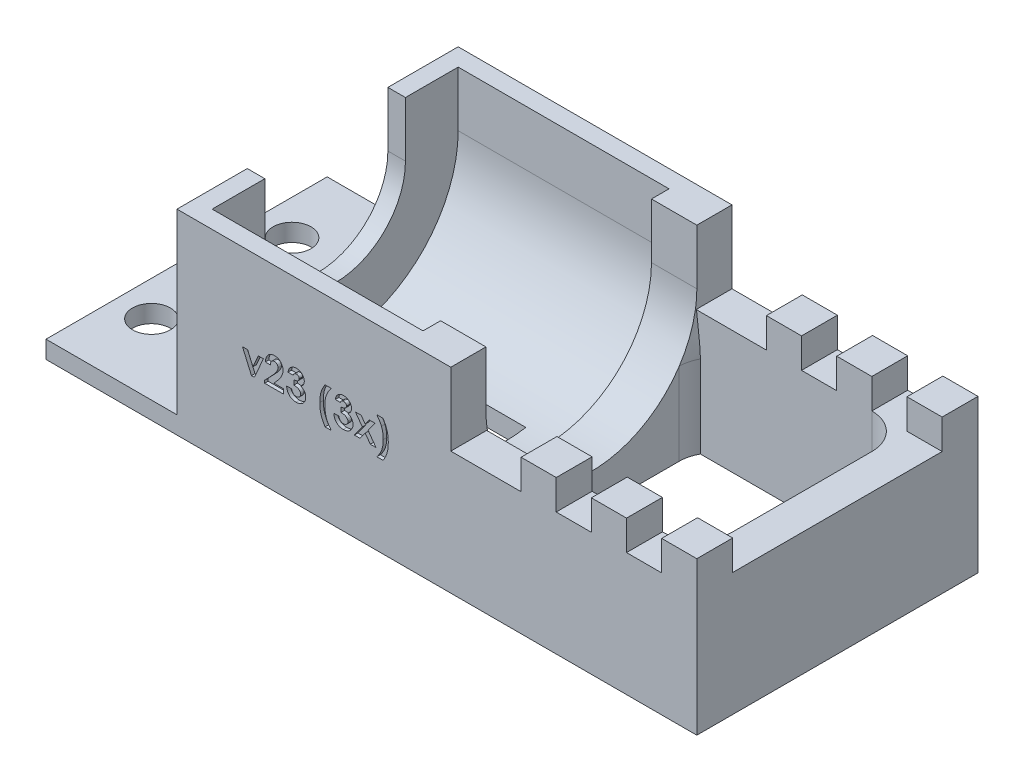
SolidWorks part; units mm, degrees
ref_plane "Front Plane" through (0, 0, 0) normal (0, 0, 1) x (1, 0, 0)
ref_plane "Top Plane" through (0, 0, 0) normal (0, 1, 0) x (1, 0, 0)
ref_plane "Right Plane" through (0, 0, 0) normal (1, 0, 0) x (0, 0, -1)
sketch "Sketch1" plane through (0, 0, 0) normal (0, 0, 1) x (1, 0, 0)
  line L1 (-76.2, -50.8) -> (76.2, -50.8)
  line L2 (-76.2, -50.8) -> (-76.2, 0)
  line L3 (-76.2, 0) -> (76.2, 0)
  line L4 (76.2, -50.8) -> (76.2, 0)
  line L5 (-76.2, -50.8) -> (76.2, 0) construction
  line L6 (-76.2, 0) -> (76.2, -50.8) construction
  point P0 (0, 0)
  dimension "D1" = 152.4
  dimension "D2" = 50.8
  dimension "D3" = 76.2
extrude "Boss-Extrude1" add sketch "Sketch1" along normal mid plane 50.8
sketch "Sketch2" plane through (0, 0, 0) normal (0, 0, 1) x (1, 0, 0)
  line L0 (-152.4829, -25.4) -> (19.6294, -25.4) construction
  line L1 (-49.3609, -3.175) -> (-49.3609, -12.7)
  line L2 (76.2, 0) -> (-76.2, 0) construction
  line L3 (76.2, 0) -> (-76.2, 0) construction
  line L4 (-11.2609, -3.175) -> (-11.2609, -6.35)
  line L5 (-11.2609, -25.4) -> (-11.2609, -3.175) construction
  line L6 (-128.4172, -25.4) -> (-157.8092, -25.4)
  line L7 (19.6294, -25.4) -> (20.7431, -25.4)
  line L8 (-607.3619, -25.4) -> (19.6294, -25.4) construction
  line L9 (-49.3609, -3.175) -> (-11.2609, -3.175)
  line L10 (19.6294, -25.4) -> (-128.4172, -25.4)
  line L11 (-11.2609, -6.35) -> (-4.6569, -6.35)
  line L12 (-4.6569, -6.35) -> (-4.6569, -15.494)
  line L13 (-4.6569, -15.494) -> (20.7431, -15.494)
  line L14 (-49.3609, -12.7) -> (-220.2024, -12.7)
  line L15 (-220.2024, -12.7) -> (-220.2024, -25.4)
  line L16 (-220.2024, -25.4) -> (-157.8092, -25.4)
  line L20 (20.7431, -15.494) -> (20.7431, -25.4)
  line L21 (-76.2, 0) -> (-76.2, -50.8) construction
  point P23 (-11.2609, -25.4)
  dimension "D1" = 22.225
  dimension "D2" = 38.1
  dimension "D3" = 25.4
  dimension "D4" = 32.004
  dimension "D5" = 9.906
  dimension "D6" = 3.175
  dimension "D7" = 26.8391
  dimension "D8" = 25.4
  dimension "D9" = 12.7
revolve "Cut-Revolve1" cut sketch "Sketch2" angle 360 about L0
sketch "Sketch38" plane through (20.7431, 0, 0) normal (1, 0, 0) x (0, 0, -1)
  line L1 (-10, -35.4) -> (10, -35.4)
  line L2 (-10, -35.4) -> (-10, -15.4)
  line L3 (-10, -15.4) -> (10, -15.4)
  line L4 (10, -35.4) -> (10, -15.4)
  line L5 (-10, -35.4) -> (10, -15.4) construction
  line L6 (-10, -15.4) -> (10, -35.4) construction
  circle A0 centre (0, -25.4) radius 9.906 construction
  point P1 (0, -25.4)
  dimension "D1" = 20
  dimension "D2" = 20
extrude "Cut-Extrude33" cut sketch "Sketch38" against normal offset from surface (23.8125 mm away) 1.5875 up to face at (-4.6569, -25.4, 19.05)
sketch "Sketch37" plane through (76.2, 0, 0) normal (1, 0, 0) x (0, 0, -1)
  line L0 (25.4, -50.8) -> (25.4, 0) construction
  line L1 (-25.4, 0) -> (25.4, 0)
  line L2 (-25.4, 0) -> (-25.4, -25.4)
  line L3 (-25.4, -25.4) -> (25.4, -25.4)
  line L4 (25.4, 0) -> (25.4, -25.4)
  line L5 (10, -35.4) -> (10, -15.4) construction
  point P7 (0, -25.4)
  point P11 (0, 0)
  point P14 (10, -25.4)
extrude "Cut-Extrude32" cut sketch "Sketch37" against normal through all
sketch "Sketch39" plane through (0, -25.4, 0) normal (0, 1, 0) x (1, 0, 0)
  line L24 (-49.3609, -12.7) -> (-76.2, -12.7)
  line L25 (-76.2, -12.7) -> (-76.2, -25.4)
  line L26 (-76.2, -25.4) -> (76.2, -25.4)
  line L27 (76.2, -25.4) -> (76.2, 25.4)
  line L28 (76.2, 25.4) -> (-76.2, 25.4)
  line L29 (-76.2, 25.4) -> (-76.2, 12.7)
  line L30 (-76.2, 12.7) -> (-49.3609, 12.7)
  line L31 (-49.3609, 12.7) -> (-49.3609, 22.225)
  line L32 (-49.3609, 22.225) -> (-11.2609, 22.225)
  line L33 (-11.2609, 22.225) -> (-11.2609, 19.05)
  line L34 (-11.2609, 19.05) -> (-4.6569, 19.05)
  line L35 (-4.6569, 19.05) -> (-4.6569, 9.906)
  line L36 (-4.6569, 9.906) -> (-3.0694, 9.906)
  line L37 (-3.0694, 9.906) -> (-3.0694, 10)
  line L38 (-3.0694, 9.906) -> (-3.0694, 10)
  line L39 (20.7431, 10) -> (20.7431, -10)
  line L40 (-3.0694, 10) -> (20.7431, 10)
  line L41 (-3.0694, 10) -> (20.7431, 10)
  line L42 (-3.0694, -9.906) -> (-4.6569, -9.906)
  line L43 (-4.6569, -9.906) -> (-4.6569, -19.05)
  line L44 (-4.6569, -19.05) -> (-11.2609, -19.05)
  line L45 (-11.2609, -19.05) -> (-11.2609, -22.225)
  line L46 (-11.2609, -22.225) -> (-49.3609, -22.225)
  line L47 (-49.3609, -22.225) -> (-49.3609, -12.7)
  line L48 (-49.3609, -12.7) -> (-76.2, -12.7)
  line L49 (-76.2, -12.7) -> (-76.2, -25.4)
  line L50 (-76.2, -25.4) -> (76.2, -25.4)
  line L51 (76.2, -25.4) -> (76.2, 25.4)
  line L52 (76.2, 25.4) -> (-76.2, 25.4)
  line L53 (-76.2, 25.4) -> (-76.2, 12.7)
  line L54 (-76.2, 12.7) -> (-49.3609, 12.7)
  line L55 (-49.3609, 12.7) -> (-49.3609, 22.225)
  line L56 (-49.3609, 22.225) -> (-11.2609, 22.225)
  line L57 (-11.2609, 22.225) -> (-11.2609, 19.05)
  line L58 (-11.2609, 19.05) -> (-4.6569, 19.05)
  line L59 (-4.6569, 19.05) -> (-4.6569, 9.906)
  line L60 (-4.6569, 9.906) -> (-3.0694, 9.906)
  line L61 (20.7431, -10) -> (-3.0694, -10)
  line L62 (20.7431, -10) -> (-3.0694, -10)
  line L63 (20.7431, 10) -> (20.7431, -10)
  line L64 (-3.0694, -10) -> (-3.0694, -9.906)
  line L65 (-3.0694, -10) -> (-3.0694, -9.906)
  line L66 (-3.0694, -9.906) -> (-4.6569, -9.906)
  line L67 (-4.6569, -9.906) -> (-4.6569, -19.05)
  line L68 (-4.6569, -19.05) -> (-11.2609, -19.05)
  line L69 (-11.2609, -19.05) -> (-11.2609, -22.225)
  line L70 (-11.2609, -22.225) -> (-49.3609, -22.225)
  line L71 (-49.3609, -22.225) -> (-49.3609, -12.7)
  dimension "D1" = 0
extrude "Boss-Extrude5" add sketch "Sketch39" along normal blind 25.4
ref_axis "Axis1" through (-3.0694, -25.4, 0) along (-1, 0, 0)
ref_plane "Plane_Mid" through (0, -25.4, 0) normal (0, 1, 0) x (1, 0, 0)
sketch "Sketch45" plane through (0, 0, 0) normal (0, 0, 1) x (1, 0, 0)
  line L2 (76.2, 0) -> (-3.0694, 0)
  line L4 (76.2, 0) -> (76.2, -19.05)
  line L5 (76.2, -19.05) -> (-3.0694, -19.05)
  line L6 (-3.0694, -25.4) -> (-4.6569, -25.4) construction
  line L8 (-3.0694, 0) -> (-3.0694, -19.05)
  dimension "D2" = 6.35
extrude "Cut-Extrude54" cut sketch "Sketch45" against normal through all both and the other way through all
sketch "Sketch53" plane through (20.7431, 0, 0) normal (-1, 0, 0) x (0, 0, 1)
  circle A0 centre (0, -25.4) radius 2
  dimension "D1" = 4
extrude "Cut-Extrude46" cut sketch "Sketch53" against normal blind 0.0254
sketch "Sketch72" plane through (0, -19.05, 0) normal (0, 1, 0) x (1, 0, 0)
  line L0 (-3.0694, -25.4) -> (-3.0694, -13.175)
  line L1 (-3.0694, -10) -> (-3.0694, -25.4) construction
  line L2 (-3.0694, -13.175) -> (23.9181, -13.175)
  line L3 (23.9181, -13.175) -> (23.9181, 13.175)
  line L4 (23.9181, 13.175) -> (-3.0694, 13.175)
  line L5 (-3.0694, 25.4) -> (-3.0694, 10) construction
  line L6 (-3.0694, 13.175) -> (-3.0694, 25.4)
  line L7 (-3.0694, 25.4) -> (76.2, 25.4)
  line L8 (76.2, 25.4) -> (76.2, -25.4)
  line L9 (76.2, -25.4) -> (-3.0694, -25.4)
  line L10 (-3.0694, -10) -> (20.7431, -10) construction
  line L11 (-3.0694, -10) -> (-3.0694, -13.175) construction
  line L12 (20.7431, -10) -> (23.9181, -10) construction
  line L13 (20.7431, 10) -> (20.7431, 13.175) construction
  dimension "D1" = 3.175
sketch "Sketch61" plane through (-4.6569, 0, 0) normal (-1, 0, 0) x (0, 0, 1)
  circle A0 centre (0, -25.4) radius 9.525
  circle A1 centre (0, -25.4) radius 9.906
  arc A2 (-9.906, -25.4) -> (9.906, -25.4) centre (0, -25.4) ccw construction
  dimension "D1" = 19.05
extrude "Boss-Extrude11" add sketch "Sketch61" against normal up to surface (1.5875 mm away) up to face at (-3.0694, -17.3088, 0)
sketch "Sketch70" plane through (0, 0, 0) normal (0, 1, 0) x (1, 0, 0)
  line L1 (-4.6569, 9.906) -> (-3.0694, 9.906)
  line L2 (-4.6569, 9.906) -> (-4.6569, -9.906)
  line L3 (-4.6569, -9.906) -> (-3.0694, -9.906)
  line L4 (-3.0694, 9.906) -> (-3.0694, -9.906)
extrude "Boss-Extrude17" add sketch "Sketch70" against normal up to next
sketch "Sketch76" plane through (0, -35.4, 0) normal (0, 1, 0) x (1, 0, 0)
  line L5 (-3.0694, -10) -> (20.7431, -10)
  line L6 (20.7431, -10) -> (20.7431, 10)
  line L9 (20.7431, 10) -> (-3.0694, 10)
  line L10 (-3.0694, 10) -> (-3.0694, -10)
  line L11 (-3.0694, -10) -> (20.7431, -10)
  line L12 (20.7431, -10) -> (20.7431, 10)
  line L13 (20.7431, 10) -> (-3.0694, 10)
  line L14 (-3.0694, 10) -> (-3.0694, -10)
  dimension "D1" = 0
extrude "Cut-Extrude58" cut sketch "Sketch76" against normal through all
sketch "Sketch86" plane through (0, -19.05, 0) normal (0, 1, 0) x (1, 0, 0)
  line L8 (-3.0694, -25.4) -> (76.2, -25.4)
  line L9 (-3.0694, -25.4) -> (76.2, -25.4)
  line L10 (76.2, -25.4) -> (76.2, 25.4)
  line L11 (76.2, -25.4) -> (76.2, 25.4)
  line L12 (76.2, 25.4) -> (-3.0694, 25.4)
  line L13 (76.2, 25.4) -> (-3.0694, 25.4)
  line L16 (20.7431, 10) -> (20.7431, -10)
  line L25 (20.7431, -10) -> (-3.0694, -10)
  line L26 (-3.0694, -10) -> (-3.0694, -25.4)
  line L30 (-3.0694, 25.4) -> (-3.0694, 10)
  line L31 (-3.0694, 10) -> (20.7431, 10)
  line L32 (20.7431, 10) -> (20.7431, -10)
  line L41 (20.7431, -10) -> (-3.0694, -10)
  line L42 (-3.0694, -10) -> (-3.0694, -25.4)
  line L46 (-3.0694, 25.4) -> (-3.0694, 10)
  line L47 (-3.0694, 10) -> (20.7431, 10)
  dimension "D1" = 0
extrude "Boss-Extrude24" add sketch "Sketch86" along normal blind 3.175
ref_plane "Plane1" through (-74.7609, 0, 0) normal (1, 0, 0) x (0, 0, -1)
sketch "Sketch89" plane through (0, 0, 0) normal (0, 1, 0) x (1, 0, 0)
  line L0 (-3.0694, 0) -> (-4.6569, 0) construction
  line L1 (-38.3605, -3.81) -> (-18.7213, -3.81)
  line L2 (-38.3605, -3.81) -> (-38.3605, 3.81)
  line L3 (-38.3605, 3.81) -> (-18.7213, 3.81)
  line L4 (-18.7213, -3.81) -> (-18.7213, 3.81)
  line L5 (-38.3605, -3.81) -> (-18.7213, 3.81) construction
  line L6 (-38.3605, 3.81) -> (-18.7213, -3.81) construction
  point P4 (-28.5409, 0)
extrude "Cut-Extrude64" cut sketch "Sketch89" against normal through all both and the other way through all
sketch "Sketch77" plane through (0, 0, 0) normal (0, 0, 1) x (1, 0, 0)
  line L0 (20.7431, -24.0284) -> (23.9181, -24.0284)
  line L1 (-3.0694, -26.7716) -> (20.7431, -26.7716)
  line L2 (-3.0694, -26.7716) -> (-3.0694, -24.0284)
  line L3 (-3.0694, -24.0284) -> (20.7431, -24.0284)
  line L4 (20.7431, -26.7716) -> (20.7431, -24.0284) construction
  line L5 (-3.0694, -26.7716) -> (20.7431, -24.0284) construction
  line L6 (-3.0694, -24.0284) -> (20.7431, -26.7716) construction
  line L7 (23.9181, -24.0284) -> (23.9181, -26.7716)
  line L8 (23.9181, -26.7716) -> (20.7431, -26.7716)
  line L9 (-3.0694, -25.4) -> (-4.6569, -25.4) construction
  line L10 (-3.0694, -15.875) -> (-3.0694, -50.8) construction
  line L11 (20.7431, -15.875) -> (20.7431, -50.8) construction
  point P0 (8.8368, -25.4)
  dimension "D1" = 3.175
  dimension "D2" = 2.7432
extrude "Cut-Extrude59" cut sketch "Sketch77" against normal through all both and the other way through all
sketch "Sketch96" plane through (0, 0, 25.4) normal (0, 0, 1) x (1, 0, 0)
  line L0 (-39.6347, 0) -> (-39.6347, -50.8) construction
  line L1 (-76.2, 0) -> (-3.0694, 0) construction
  line L2 (-76.2, -50.8) -> (76.2, -50.8) construction
  line L3 (-55.5097, -15.4427) -> (-23.7597, -15.4427)
  arc A0 (-23.7597, -15.4427) -> (-55.5097, -15.4427) centre (-39.6347, -32.1115) ccw
  point P8 (-39.6347, -15.4427)
  point P10 (-39.6347, -9.0927)
  dimension "D2" = 6.35
  dimension "D1" = 31.75
extrude "Cut-Extrude71" cut sketch "Sketch96" against normal through all
sketch "Sketch97" plane through (0, 0, 0) normal (0, 1, 0) x (1, 0, 0)
  line L0 (-76.2, -25.4) -> (-3.0694, -25.4) construction
  line L1 (-76.2, 25.4) -> (-52.5359, 25.4)
  line L2 (-76.2, 25.4) -> (-76.2, -25.4)
  line L3 (-76.2, -25.4) -> (-52.5359, -25.4)
  line L4 (-52.5359, 25.4) -> (-52.5359, -25.4)
  line L5 (-49.3609, 12.7) -> (-49.3609, 22.225) construction
  dimension "D1" = 3.175
extrude "Cut-Extrude72" cut sketch "Sketch97" against normal offset from surface (47.625 mm away) 3.175 up to face at (-28.5409, -50.8, 0)
sketch "Sketch98" plane through (0, -47.625, 0) normal (0, 1, 0) x (1, 0, 0)
  line L0 (-76.2, -25.4) -> (-76.2, 25.4) construction
  circle A0 centre (-69.85, 12.7) radius 3.429
  circle A1 centre (-57.15, 12.7) radius 3.429
  circle A2 centre (-57.15, 0) radius 3.429
  circle A3 centre (-57.15, -12.7) radius 3.429
  circle A4 centre (-69.85, 0) radius 3.429
  circle A5 centre (-69.85, -12.7) radius 3.429
  dimension "D1" = 6.858
  dimension "D2" = 76.2
  dimension "D3" = 6.35
  dimension "D4" = 12.7
  dimension "D5" = 2
  dimension "D6" = 3
extrude "Cut-Extrude73" cut sketch "Sketch98" against normal through all
ref_plane "Plane2" through (0, -25.4, 0) normal (0, 1, 0) x (1, 0, 0)
sketch "Sketch99" plane through (0, -25.4, 0) normal (0, 1, 0) x (1, 0, 0)
  line L1 (-3.0694, -25.4) -> (76.2, -25.4)
  line L2 (-3.0694, -25.4) -> (-3.0694, 25.4)
  line L3 (-3.0694, 25.4) -> (76.2, 25.4)
  line L4 (76.2, -25.4) -> (76.2, 25.4)
extrude "Cut-Extrude74" cut sketch "Sketch99" along normal through all
sketch "Sketch100" plane through (0, -25.4, 0) normal (0, 1, 0) x (1, 0, 0)
  line L0 (-3.0694, -25.4) -> (23.9181, -25.4) construction
  line L1 (-3.0694, -25.4) -> (76.2, -25.4)
  line L2 (-3.0694, -25.4) -> (-3.0694, 25.4)
  line L3 (-3.0694, 25.4) -> (76.2, 25.4)
  line L4 (76.2, -25.4) -> (76.2, 25.4)
  line L5 (-3.0694, 25.4) -> (76.2, 25.4) construction
  line L6 (-3.0694, -10) -> (-3.0694, -25.4) construction
extrude "Cut-Extrude75" cut sketch "Sketch100" against normal blind 2.2225
sketch "Sketch101" plane through (0, -25.4, 0) normal (0, 1, 0) x (1, 0, 0)
  line L0 (-3.0694, 25.4) -> (76.2, 25.4) construction
  line L1 (47.7306, 25.4) -> (52.3026, 25.4)
  line L2 (47.7306, 25.4) -> (47.7306, -25.4)
  line L3 (47.7306, -25.4) -> (52.3026, -25.4)
  line L4 (52.3026, 25.4) -> (52.3026, -25.4)
  line L6 (-3.0694, -25.4) -> (-3.0694, -13.175) construction
  dimension "D1" = 4.572
  dimension "D2" = 50.8
extrude "Cut-Extrude76" cut sketch "Sketch101" against normal blind 6.0579
sketch "Sketch103" plane through (0, -27.6225, 0) normal (0, 1, 0) x (1, 0, 0)
  line L0 (-3.0694, -25.4) -> (-3.0694, -13.175) construction
  line L1 (-3.0694, 0) -> (-4.6569, 0) construction
  line L2 (41.3806, 22.225) -> (-3.0694, 22.225)
  line L3 (41.3806, 22.225) -> (41.3806, -22.225)
  line L4 (41.3806, -22.225) -> (-3.0694, -22.225)
  line L5 (-3.0694, 22.225) -> (-3.0694, -22.225)
  line L6 (-3.0694, 25.4) -> (76.2, 25.4) construction
  line L7 (47.7306, -25.4) -> (47.7306, 25.4) construction
  point P6 (41.3806, 0)
  dimension "D1" = 3.175
  dimension "D2" = 6.35
extrude "Cut-Extrude78" cut sketch "Sketch103" against normal through all
sketch "Sketch104" plane through (-4.6569, 0, 0) normal (-1, 0, 0) x (0, 0, 1)
  line L3 (19.05, -25.4) -> (19.05, 0)
  line L4 (19.05, 0) -> (-19.05, 0)
  line L5 (-19.05, 0) -> (-19.05, -25.4)
  line L6 (19.05, -25.4) -> (19.05, 0)
  line L7 (19.05, 0) -> (-19.05, 0)
  line L8 (-19.05, 0) -> (-19.05, -25.4)
  arc A1 (-19.05, -25.4) -> (19.05, -25.4) centre (0, -25.4) ccw
  arc A2 (-19.05, -25.4) -> (19.05, -25.4) centre (0, -25.4) ccw
  dimension "D1" = 0
extrude "Cut-Extrude79" cut sketch "Sketch104" against normal up to next
sketch "Sketch105" plane through (0, -50.8, 0) normal (0, 1, 0) x (1, 0, 0)
  line L0 (41.3806, 22.225) -> (-3.0694, 22.225) construction
  line L1 (-3.0694, 22.225) -> (41.3806, 22.225)
  line L2 (-3.0694, 22.225) -> (-3.0694, 47.625)
  line L3 (-3.0694, 47.625) -> (41.3806, 47.625)
  line L4 (41.3806, 22.225) -> (41.3806, 47.625)
  line L5 (0, 0) -> (31.7243, 0) construction
  line L6 (-3.0694, 19.05) -> (-3.0694, 25.4) construction
  line L7 (41.3806, -22.225) -> (41.3806, 22.225) construction
  line L8 (41.3806, -22.225) -> (41.3806, -47.625)
  line L9 (-3.0694, -47.625) -> (41.3806, -47.625)
  line L10 (-3.0694, -22.225) -> (-3.0694, -47.625)
  line L11 (-3.0694, -22.225) -> (41.3806, -22.225)
  dimension "D1" = 25.4
extrude "Boss-Extrude25" add sketch "Sketch105" along normal up to surface (23.1775 mm away) up to face at (20.7431, -27.6225, 0)
sketch "Sketch106" plane through (0, -27.6225, 0) normal (0, 1, 0) x (1, 0, 0)
  line L0 (76.2, 25.4) -> (52.3026, 25.4) construction
  line L1 (76.2, 25.4) -> (58.6526, 25.4)
  line L2 (76.2, 25.4) -> (76.2, -25.4)
  line L3 (76.2, -25.4) -> (58.6526, -25.4)
  line L4 (58.6526, 25.4) -> (58.6526, -25.4)
  line L5 (76.2, -25.4) -> (76.2, 25.4) construction
  line L6 (52.3026, -25.4) -> (76.2, -25.4) construction
  line L7 (52.3026, -25.4) -> (52.3026, 25.4) construction
  dimension "D1" = 6.35
extrude "Cut-Extrude80" cut sketch "Sketch106" against normal through all
fillet "Fillet1" radius 6.35 14 edges at (-3.0694, -39.2112, -47.625) (41.3806, -39.2112, -47.625) (41.3806, -39.2112, -25.4) (58.6526, -39.2112, -25.4) (58.6526, -39.2112, 25.4) (41.3806, -39.2112, 25.4) (41.3806, -39.2112, 47.625) (-3.0694, -39.2112, 47.625) (-3.0694, -39.2112, 25.4) (-3.0694, -39.2112, 22.225) (-3.0694, -39.2112, -22.225) (41.3806, -39.2112, -22.225) (41.3806, -39.2112, 22.225) (-3.0694, -39.2112, -25.4)
sketch "Sketch107" plane through (0, -27.6225, 0) normal (0, 1, 0) x (1, 0, 0)
  line L0 (47.7306, -25.4) -> (47.7306, 25.4) construction
  line L1 (22.3306, 47.625) -> (47.7306, 47.625)
  line L2 (22.3306, 47.625) -> (22.3306, 6.35)
  line L3 (22.3306, 6.35) -> (47.7306, 6.35)
  line L4 (47.7306, 47.625) -> (47.7306, 6.35)
  line L5 (3.2806, 47.625) -> (35.0306, 47.625) construction
  line L6 (0, 0) -> (41.3806, 0) construction
  line L7 (41.3806, -15.875) -> (41.3806, 15.875) construction
  line L8 (47.7306, -47.625) -> (47.7306, -6.35)
  line L9 (22.3306, -6.35) -> (47.7306, -6.35)
  line L10 (22.3306, -47.625) -> (22.3306, -6.35)
  line L11 (22.3306, -47.625) -> (47.7306, -47.625)
  dimension "D1" = 25.4
  dimension "D2" = 6.35
extrude "Cut-Extrude81" cut sketch "Sketch107" against normal up to surface (3.8354 mm away) up to face at (50.0166, -31.4579, 0)
sketch "Sketch108" plane through (0, -15.4427, 0) normal (0, 1, 0) x (1, 0, 0)
  line L0 (-52.5359, -25.4) -> (-23.7597, -25.4) construction
  line L1 (-52.5359, -25.4) -> (14.8431, -25.4)
  line L2 (-52.5359, -25.4) -> (-52.5359, 39.7712)
  line L3 (-52.5359, 39.7712) -> (14.8431, 39.7712)
  line L4 (14.8431, -25.4) -> (14.8431, 39.7712)
extrude "Cut-Extrude82" cut sketch "Sketch108" along normal through all
sketch "Sketch109" plane through (0, -31.4579, 0) normal (0, 1, 0) x (1, 0, 0)
  line L16 (52.3026, 25.4) -> (47.7306, 25.4)
  line L17 (41.3806, 31.75) -> (41.3806, 41.275)
  line L18 (35.0306, 47.625) -> (22.3306, 47.625)
  line L19 (22.3306, 47.625) -> (22.3306, 22.225)
  line L20 (22.3306, 22.225) -> (35.0306, 22.225)
  line L21 (41.3806, 15.875) -> (41.3806, 6.35)
  line L22 (41.3806, 6.35) -> (47.7306, 6.35)
  line L23 (47.7306, 6.35) -> (47.7306, -6.35)
  line L24 (47.7306, -6.35) -> (41.3806, -6.35)
  line L25 (41.3806, -6.35) -> (41.3806, -15.875)
  line L26 (35.0306, -22.225) -> (22.3306, -22.225)
  line L27 (22.3306, -22.225) -> (22.3306, -47.625)
  line L28 (22.3306, -47.625) -> (35.0306, -47.625)
  line L29 (41.3806, -41.275) -> (41.3806, -31.75)
  line L30 (47.7306, -25.4) -> (52.3026, -25.4)
  line L31 (52.3026, -25.4) -> (52.3026, 25.4)
  line L32 (52.3026, 25.4) -> (47.7306, 25.4)
  line L33 (41.3806, 31.75) -> (41.3806, 41.275)
  line L34 (35.0306, 47.625) -> (22.3306, 47.625)
  line L35 (22.3306, 47.625) -> (22.3306, 22.225)
  line L36 (22.3306, 22.225) -> (35.0306, 22.225)
  line L37 (41.3806, 15.875) -> (41.3806, 6.35)
  line L38 (41.3806, 6.35) -> (47.7306, 6.35)
  line L39 (47.7306, 6.35) -> (47.7306, -6.35)
  line L40 (47.7306, -6.35) -> (41.3806, -6.35)
  line L41 (41.3806, -6.35) -> (41.3806, -15.875)
  line L42 (35.0306, -22.225) -> (22.3306, -22.225)
  line L43 (22.3306, -22.225) -> (22.3306, -47.625)
  line L44 (22.3306, -47.625) -> (35.0306, -47.625)
  line L45 (41.3806, -41.275) -> (41.3806, -31.75)
  line L46 (47.7306, -25.4) -> (52.3026, -25.4)
  line L47 (52.3026, -25.4) -> (52.3026, 25.4)
  arc A6 (41.3806, 31.75) -> (47.7306, 25.4) centre (47.7306, 31.75) ccw
  arc A7 (41.3806, 41.275) -> (35.0306, 47.625) centre (35.0306, 41.275) ccw
  arc A8 (41.3806, 15.875) -> (35.0306, 22.225) centre (35.0306, 15.875) ccw
  arc A9 (35.0306, -22.225) -> (41.3806, -15.875) centre (35.0306, -15.875) ccw
  arc A10 (35.0306, -47.625) -> (41.3806, -41.275) centre (35.0306, -41.275) ccw
  arc A11 (47.7306, -25.4) -> (41.3806, -31.75) centre (47.7306, -31.75) ccw
  arc A12 (41.3806, 31.75) -> (47.7306, 25.4) centre (47.7306, 31.75) ccw
  arc A13 (41.3806, 41.275) -> (35.0306, 47.625) centre (35.0306, 41.275) ccw
  arc A14 (41.3806, 15.875) -> (35.0306, 22.225) centre (35.0306, 15.875) ccw
  arc A15 (35.0306, -22.225) -> (41.3806, -15.875) centre (35.0306, -15.875) ccw
  arc A16 (35.0306, -47.625) -> (41.3806, -41.275) centre (35.0306, -41.275) ccw
  arc A17 (47.7306, -25.4) -> (41.3806, -31.75) centre (47.7306, -31.75) ccw
  dimension "D1" = 0
extrude "Boss-Extrude26" add sketch "Sketch109" along normal up to surface (3.8354 mm away) up to face at (56.1352, -27.6225, 0)
ref_point "Point1"
sketch "Sketch110" plane through (0, 0, 25.4) normal (0, 0, 1) x (1, 0, 0)
  line L1 (-76.2, -50.8) -> (82.1267, -50.8)
  line L2 (-76.2, -50.8) -> (-76.2, 4.0878)
  line L3 (-76.2, 4.0878) -> (82.1267, 4.0878)
  line L4 (82.1267, -50.8) -> (82.1267, 4.0878)
extrude "Cut-Extrude83" cut sketch "Sketch110" along normal through all
sketch "Sketch111" plane through (0, 0, -25.4) normal (0, 0, -1) x (-1, 0, 0)
  line L1 (76.2, -50.8) -> (-87.2258, -50.8)
  line L2 (76.2, -50.8) -> (76.2, 6.8745)
  line L3 (76.2, 6.8745) -> (-87.2258, 6.8745)
  line L4 (-87.2258, -50.8) -> (-87.2258, 6.8745)
extrude "Cut-Extrude84" cut sketch "Sketch111" along normal through all
sketch "Sketch112" plane through (0, -27.6225, 0) normal (0, 1, 0) x (1, 0, 0)
  line L1 (45.4111, -23.0804) -> (-3.0694, -23.0804)
  line L2 (45.4111, -23.0804) -> (45.4111, -18.9199)
  line L3 (45.4111, -18.9199) -> (-3.0694, -18.9199)
  line L4 (-3.0694, -23.0804) -> (-3.0694, -18.9199)
extrude "Boss-Extrude27" add sketch "Sketch112" against normal up to surface (23.1775 mm away) up to face at (-28.5409, -50.8, 0)
sketch "Sketch113" plane through (0, -27.6225, 0) normal (0, 1, 0) x (1, 0, 0)
  line L0 (-3.0694, 25.4) -> (-3.0694, 18.9199) construction
  line L1 (44.686, 23.4931) -> (-3.0694, 23.4931)
  line L2 (44.686, 23.4931) -> (44.686, 18.9199)
  line L3 (44.686, 18.9199) -> (-3.0694, 18.9199)
  line L4 (-3.0694, 23.4931) -> (-3.0694, 18.9199)
  spline S0 degree 3 poles (-3.0694, 18.9199) (-2.7943, 19.4222) (-2.4587, 19.8766) (-1.8671, 20.4883) (-1.6535, 20.6814) (-1.2078, 21.0329) (-0.9747, 21.1925) (-0.2456, 21.624) (0.2875, 21.8498) (1.105, 22.0734) (1.3817, 22.1298) (1.9436, 22.2056) (2.2301, 22.225) (2.5164, 22.225) knots 0 0 0 0 0.25 0.25 0.375 0.375 0.5 0.5 0.75 0.75 0.875 0.875 1 1 1 1 construction
extrude "Boss-Extrude28" add sketch "Sketch113" against normal up to surface (23.1775 mm away) up to face at (19.1556, -50.8, -1.1428)
sketch "Sketch117" plane through (0, -27.6225, 0) normal (0, 1, 0) x (1, 0, 0)
  line L0 (-3.0694, 25.4) -> (-3.0694, 19.05) construction
  line L1 (-3.0694, 49.9635) -> (72.0105, 49.9635)
  line L2 (-3.0694, 49.9635) -> (-3.0694, -40.6416)
  line L3 (-3.0694, -40.6416) -> (72.0105, -40.6416)
  line L4 (72.0105, 49.9635) -> (72.0105, -40.6416)
sketch "Sketch120" plane through (0, -27.6225, 0) normal (0, 1, 0) x (1, 0, 0)
  line L8 (-3.0694, 18.9199) -> (40.6029, 18.9199)
  line L9 (41.3806, 15.875) -> (41.3806, -15.875)
  line L10 (40.6029, -18.9199) -> (-3.0694, -18.9199)
  line L11 (-3.0694, -18.9199) -> (-3.0694, -25.4)
  line L12 (-3.0694, -25.4) -> (52.3026, -25.4)
  line L13 (58.6526, -19.05) -> (58.6526, 19.05)
  line L14 (52.3026, 25.4) -> (-3.0694, 25.4)
  line L15 (-3.0694, 25.4) -> (-3.0694, 18.9199)
  line L16 (-3.0694, 18.9199) -> (40.6029, 18.9199)
  line L17 (41.3806, 15.875) -> (41.3806, -15.875)
  line L18 (40.6029, -18.9199) -> (-3.0694, -18.9199)
  line L19 (-3.0694, -18.9199) -> (-3.0694, -25.4)
  line L20 (-3.0694, -25.4) -> (52.3026, -25.4)
  line L21 (58.6526, -19.05) -> (58.6526, 19.05)
  line L22 (52.3026, 25.4) -> (-3.0694, 25.4)
  line L23 (-3.0694, 25.4) -> (-3.0694, 18.9199)
  arc A4 (41.3806, 15.875) -> (40.6029, 18.9199) centre (35.0306, 15.875) ccw
  arc A5 (40.6029, -18.9199) -> (41.3806, -15.875) centre (35.0306, -15.875) ccw
  arc A6 (52.3026, -25.4) -> (58.6526, -19.05) centre (52.3026, -19.05) ccw
  arc A7 (58.6526, 19.05) -> (52.3026, 25.4) centre (52.3026, 19.05) ccw
  arc A8 (41.3806, 15.875) -> (40.6029, 18.9199) centre (35.0306, 15.875) ccw
  arc A9 (40.6029, -18.9199) -> (41.3806, -15.875) centre (35.0306, -15.875) ccw
  arc A10 (52.3026, -25.4) -> (58.6526, -19.05) centre (52.3026, -19.05) ccw
  arc A11 (58.6526, 19.05) -> (52.3026, 25.4) centre (52.3026, 19.05) ccw
  dimension "D1" = 0
extrude "Boss-Extrude31" add sketch "Sketch120" along normal blind 1.27
sketch "Sketch122" plane through (0, 0, 0) normal (0, 0, 1) x (1, 0, 0)
  line L0 (19.6294, -25.4) -> (-128.4172, -25.4) construction
  line L1 (-3.0694, -25.4) -> (58.6526, -25.4)
  line L2 (-3.0694, -25.4) -> (-3.0694, -28.575)
  line L3 (-3.0694, -28.575) -> (58.6526, -28.575)
  line L4 (58.6526, -25.4) -> (58.6526, -28.575)
  line L5 (58.6526, -26.3525) -> (58.6526, -50.8) construction
  line L6 (-3.0694, -15.4427) -> (-3.0694, -26.3525) construction
  point P6 (0, 0)
  dimension "D1" = 3.175
extrude "Cut-Extrude87" cut sketch "Sketch122" against normal through all both and the other way through all
sketch "Sketch114" plane through (0, -26.3525, 0) normal (0, 1, 0) x (1, 0, 0)
  line L0 (-3.0694, 25.4) -> (52.3026, 25.4) construction
  line L1 (9.6306, 25.4) -> (15.9806, 25.4)
  line L2 (9.6306, 25.4) -> (9.6306, 18.9199)
  line L3 (9.6306, 18.9199) -> (15.9806, 18.9199)
  line L4 (15.9806, 25.4) -> (15.9806, 18.9199)
  line L5 (-3.0694, 18.9199) -> (40.6029, 18.9199) construction
  line L6 (-3.0694, 25.4) -> (-3.0694, 19.05) construction
  line L7 (22.3306, 25.4) -> (28.6806, 25.4)
  line L8 (22.3306, 25.4) -> (22.3306, 18.9199)
  line L9 (22.3306, 18.9199) -> (28.6806, 18.9199)
  line L10 (28.6806, 25.4) -> (28.6806, 18.9199)
  line L11 (35.0306, 25.4) -> (41.3806, 25.4)
  line L12 (35.0306, 25.4) -> (35.0306, 18.9199)
  line L13 (35.0306, 18.9199) -> (41.3806, 18.9199)
  line L14 (41.3806, 25.4) -> (41.3806, 18.9199)
  line L27 (22.3306, -19.05) -> (28.6806, -19.05) [skipped]
  line L28 (22.3306, -19.05) -> (22.3306, -25.5301) [skipped]
  line L29 (22.3306, -25.5301) -> (28.6806, -25.5301) [skipped]
  line L30 (28.6806, -19.05) -> (28.6806, -25.5301) [skipped]
  line L31 (35.0306, -19.05) -> (41.3806, -19.05) [skipped]
  line L32 (35.0306, -19.05) -> (35.0306, -25.5301) [skipped]
  line L33 (35.0306, -25.5301) -> (41.3806, -25.5301) [skipped]
  line L34 (41.3806, -19.05) -> (41.3806, -25.5301) [skipped]
  line L35 (9.6306, -19.05) -> (15.9806, -19.05) [skipped]
  line L36 (9.6306, -19.05) -> (9.6306, -25.5301) [skipped]
  line L37 (9.6306, -25.5301) -> (15.9806, -25.5301) [skipped]
  line L38 (15.9806, -19.05) -> (15.9806, -25.5301) [skipped]
  dimension "D1" = 6.35
  dimension "D2" = 12.7
  dimension "D3" = 3
  dimension "D4" = 2
extrude "Boss-Extrude29" add sketch "Sketch114" along normal blind 3.175 and the other way through all
mirror "Mirror1" about plane through (0, 0, 0) normal (0, 0, 1) of "Boss-Extrude29"
sketch "Sketch118" plane through (58.6526, 0, 0) normal (1, 0, 0) x (0, 0, -1)
  line L1 (-42.1291, -63.5171) -> (70.347, -63.5171)
  line L2 (-42.1291, -63.5171) -> (-42.1291, -3.6344)
  line L3 (-42.1291, -3.6344) -> (70.347, -3.6344)
  line L4 (70.347, -63.5171) -> (70.347, -3.6344)
extrude "Cut-Extrude86" cut sketch "Sketch118" against normal up to surface (17.272 mm away) up to face at (41.3806, -25.8762, -22.16)
sketch "Sketch119" plane through (41.3806, 0, 0) normal (1, 0, 0) x (0, 0, -1)
  line L0 (25.4, -23.1775) -> (25.4, -50.8) construction
  line L1 (-25.4, -50.8) -> (25.4, -50.8)
  line L2 (-25.4, -50.8) -> (-25.4, -28.575)
  line L3 (-25.4, -28.575) -> (25.4, -28.575)
  line L4 (25.4, -50.8) -> (25.4, -28.575)
  point P7 (0, 0)
  point P8 (0, 0)
extrude "Boss-Extrude30" add sketch "Sketch119" against normal blind 6.35
fillet "Fillet2" radius 6.35 2 edges at (35.0306, -39.6875, 18.9199) (35.0306, -39.6875, -18.9199)
sketch "Sketch123" plane through (0, 0, 25.4) normal (0, 0, 1) x (1, 0, 0)
  line L0 (-52.5359, -34.7674) -> (-3.0808, -34.7674) construction
  line L1 (-52.5359, -47.625) -> (-52.5359, -15.4427) construction
  text T0 "<b>v23 (3x)</b>" font "Century Gothic" height 5.08
extrude "Cut-Extrude88" cut sketch "Sketch123" against normal blind 0.635
